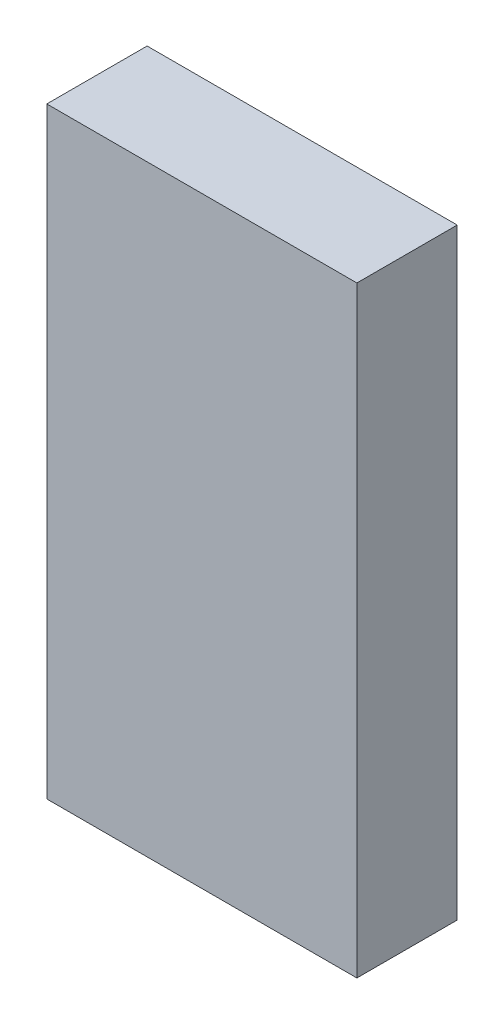
SolidWorks part; units mm, degrees
ref_plane "Front Plane" through (0, 0, 0) normal (0, 0, 1) x (1, 0, 0)
ref_plane "Top Plane" through (0, 0, 0) normal (0, 1, 0) x (1, 0, 0)
ref_plane "Right Plane" through (0, 0, 0) normal (1, 0, 0) x (0, 0, -1)
sketch "Sketch1" plane through (0, 0, 0) normal (0, 1, 0) x (1, 0, 0)
  line L0 (-36, -36) -> (36, -36)
  line L1 (46, -26) -> (46, 26)
  line L2 (36, 36) -> (-36, 36)
  line L3 (-46, 26) -> (-46, -26)
  arc A0 (46, -26) -> (36, -36) centre (36, -26) ccw
  arc A1 (36, 36) -> (46, 26) centre (36, 26) ccw
  arc A2 (-46, 26) -> (-36, 36) centre (-36, 26) ccw
  arc A3 (-36, -36) -> (-46, -26) centre (-36, -26) ccw
sketch "Sketch2" plane through (0, 0, 0) normal (0, 0, 1) x (1, 0, 0)
  circle A0 centre (-3, 13) radius 7
  circle A1 centre (-3, 13) radius 7
sketch "Sketch3" plane through (0, 0, 0) normal (0, 0, 1) x (1, 0, 0)
  line L1 (34, -33) -> (0, -33)
  line L2 (34, -33) -> (34, 33)
  line L3 (34, 33) -> (0, 33)
  line L4 (0, -33) -> (0, 33)
  line L5 (34, -33) -> (0, 33) construction
  line L6 (34, 33) -> (0, -33) construction
extrude "Boss-Extrude3" add sketch "Sketch3" against normal blind 11
sketch "Sketch4" plane through (0, 0, 0) normal (0, 0, 1) x (1, 0, 0)
  line L1 (-13, 40.1) -> (7, 40.1)
  line L2 (-13, 40.1) -> (-13, 1.9)
  line L3 (-13, 1.9) -> (7, 1.9)
  line L4 (7, 40.1) -> (7, 1.9)
  line L5 (-13, 40.1) -> (7, 1.9) construction
  line L6 (-13, 1.9) -> (7, 40.1) construction
  line L7 (5, 26.2354) -> (9, 26.2354)
  line L8 (5, 26.2354) -> (5, 6)
  line L9 (5, 6) -> (9, 6)
  line L10 (9, 26.2354) -> (9, 6)
  line L11 (5, 26.2354) -> (9, 6) construction
  line L12 (5, 6) -> (9, 26.2354) construction
  line L13 (36, 10.1) -> (7, 10.1)
  line L14 (36, 10.1) -> (36, 1.9)
  line L15 (36, 1.9) -> (7, 1.9)
  line L16 (7, 10.1) -> (7, 1.9)
  line L17 (36, 10.1) -> (7, 1.9) construction
  line L18 (36, 1.9) -> (7, 10.1) construction
  line L19 (36, 10.1) -> (7, 10.1)
  line L20 (36, 10.1) -> (36, 1.9)
  line L21 (36, 1.9) -> (7, 1.9)
  line L22 (7, 10.1) -> (7, 1.9)
  line L23 (36, 10.1) -> (7, 1.9) construction
  line L24 (36, 1.9) -> (7, 10.1) construction
  line L25 (36, 18.3) -> (7, 18.3)
  line L26 (36, 18.3) -> (36, 1.9)
  line L27 (36, 1.9) -> (7, 1.9)
  line L28 (7, 18.3) -> (7, 1.9)
  line L29 (36, 18.3) -> (7, 1.9) construction
  line L30 (36, 1.9) -> (7, 18.3) construction
  line L31 (36, 24.1) -> (7, 24.1)
  line L32 (36, 24.1) -> (36, 1.9)
  line L33 (36, 1.9) -> (7, 1.9)
  line L34 (7, 24.1) -> (7, 1.9)
  line L35 (36, 24.1) -> (7, 1.9) construction
  line L36 (36, 1.9) -> (7, 24.1) construction
  line L37 (36, 30.3354) -> (7, 30.3354)
  line L38 (36, 30.3354) -> (36, 1.9)
  line L39 (36, 1.9) -> (7, 1.9)
  line L40 (7, 30.3354) -> (7, 1.9)
  line L41 (36, 30.3354) -> (7, 1.9) construction
  line L42 (36, 1.9) -> (7, 30.3354) construction
  line L43 (32, 58.7708) -> (0, 58.7708)
  line L44 (32, 58.7708) -> (32, 1.9)
  line L45 (32, 1.9) -> (0, 1.9)
  line L46 (0, 58.7708) -> (0, 1.9)
  line L47 (32, 58.7708) -> (0, 1.9) construction
  line L48 (32, 1.9) -> (0, 58.7708) construction
  line L49 (43, 58.7708) -> (0, 58.7708)
  line L50 (43, 58.7708) -> (43, 1.9)
  line L51 (43, 1.9) -> (0, 1.9)
  line L52 (0, 58.7708) -> (0, 1.9)
  line L53 (43, 58.7708) -> (0, 1.9) construction
  line L54 (43, 1.9) -> (0, 58.7708) construction
  line L55 (46.4203, 63.2944) -> (0, 63.2944)
  line L56 (46.4203, 63.2944) -> (46.4203, 1.9)
  line L57 (46.4203, 1.9) -> (0, 1.9)
  line L58 (0, 63.2944) -> (0, 1.9)
  line L59 (46.4203, 63.2944) -> (0, 1.9) construction
  line L60 (46.4203, 1.9) -> (0, 63.2944) construction
  line L61 (56, 63.2944) -> (0, 63.2944)
  line L62 (56, 63.2944) -> (56, 1.9)
  line L63 (56, 1.9) -> (0, 1.9)
  line L64 (0, 63.2944) -> (0, 1.9)
  line L65 (56, 63.2944) -> (0, 1.9) construction
  line L66 (56, 1.9) -> (0, 63.2944) construction
  line L67 (64, 63.2944) -> (0, 63.2944)
  line L68 (64, 63.2944) -> (64, 1.9)
  line L69 (64, 1.9) -> (0, 1.9)
  line L70 (0, 63.2944) -> (0, 1.9)
  line L71 (64, 63.2944) -> (0, 1.9) construction
  line L72 (64, 1.9) -> (0, 63.2944) construction
  circle A0 centre (-3, 16.1177) radius 0.7
  circle A1 centre (-6.6, 13) radius 1.1
  circle A2 centre (-6.6, 9.8823) radius 3.6
  circle A3 centre (-3, 9.8823) radius 3
  point P8 (-3, 21)
  point P13 (7, 16.1177)
  point P18 (21.5, 6)
  point P19 (21.5, 6)
  point P23 (21.5, 10.1)
  point P24 (21.5, 13)
  point P27 (21.5, 16.1177)
  point P30 (16, 30.3354)
  point P37 (21.5, 30.3354)
  point P38 (23.2102, 32.5972)
  point P41 (28, 32.5972)
  point P45 (32, 32.5972)
